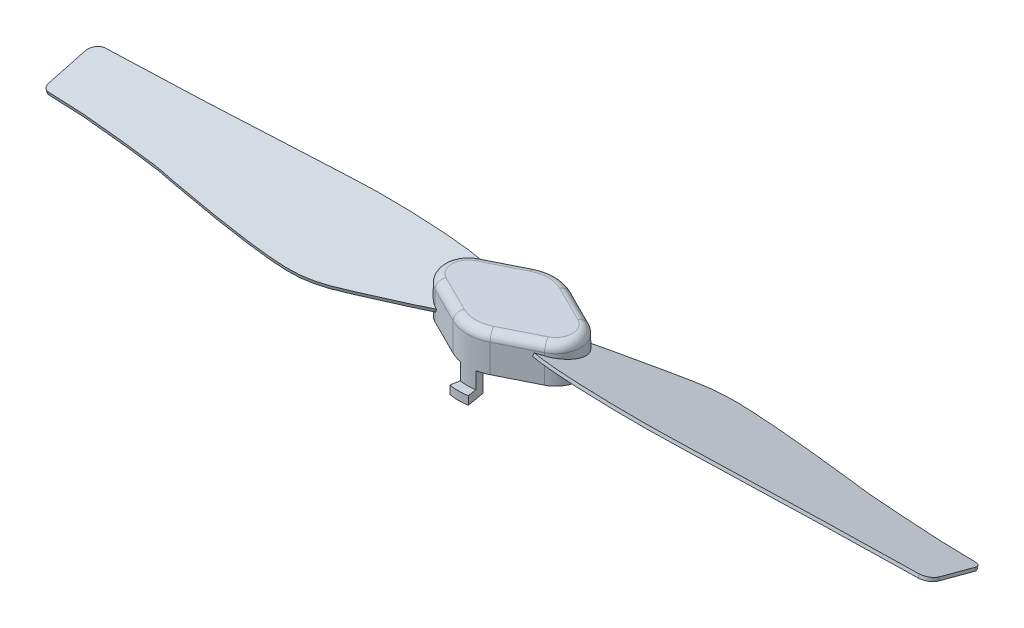
SolidWorks part; units mm, degrees
ref_plane "前视基准面" through (0, 0, 0) normal (0, 0, 1) x (1, 0, 0)
ref_plane "上视基准面" through (0, 0, 0) normal (0, 1, 0) x (1, 0, 0)
ref_plane "右视基准面" through (0, 0, 0) normal (1, 0, 0) x (0, 0, -1)
sketch "草图1" plane through (0, 0, 0) normal (0, 1, 0) x (1, 0, 0)
  line L0 (-6, 0) -> (6, 0) construction
  line L1 (0, 3) -> (0, -3) construction
  line L2 (0, 3) -> (-6, 0)
  line L3 (0, -3) -> (-6, 0)
  line L4 (0, -3) -> (6, 0)
  line L5 (6, 0) -> (0, 3)
  point P4 (0, 0)
  point P7 (0, 0)
  dimension "D1" = 12
  dimension "D2" = 6
extrude "凸台-拉伸1" add sketch "草图1" along normal blind 3.2 from offset 2
sketch "草图2" plane through (0, 2, 0) normal (0, -1, 0) x (1, 0, 0)
  line L0 (-5.2231, 0) -> (5.5973, 0)
ref_plane "基准面1" through (0, 1.866, 0.5) normal (0, -0.9659, -0.2588) x (1, 0, 0)
ref_plane "基准面10" through (0, 3.7979, 1.0176) normal (0, -0.9659, -0.2588) x (1, 0, 0)
sketch "草图9" plane through (0, 3.7979, 1.0176) normal (0, -0.9659, -0.2588) x (1, 0, 0)
  line L0 (-26.7041, 0.3228) -> (-26.7041, -1.9457)
  line L1 (0, -3.4154) -> (-6, -0.5176) construction
  line L2 (-5.2231, -0.5176) -> (5.5973, -0.5176) construction
  arc A0 (-26.7041, 0.3228) -> (-26.3393, 0.6876) centre (-26.3393, 0.3228) cw
  arc A1 (-26.7041, -1.9457) -> (-26.1115, -2.5991) centre (-26.0475, -1.9457) ccw
  spline S0 degree 3 poles (-1.4329, -0.5176) (-2.7254, 0.2749) (-2.9583, 0.3643) (-7.6949, 1.9383) (-9.1523, 2.4326) (-12.9904, 2.1706) (-15.9072, 1.7478) (-19.0984, 1.266) (-18.8037, 1.1973) (-24.7636, 0.7055) (-25.802, 0.7264) (-26.3393, 0.6876) knots 0 0 0 0 0.27319 0.324145 0.488947 0.531153 0.703993 0.748506 0.931769 0.959209 1 1 1 1
  spline S1 degree 3 poles (-26.1115, -2.5991) (-22.9105, -2.689) (-24.116, -2.6478) (-17.5523, -2.8675) (-13.3297, -3.0646) (-9.2951, -3.2316) (-3.3383, -3.0619) (-1.3944, -1.9668) (2.5094, 0.1061) (-1.4329, -0.5176) knots 0 0 0 0 0.213914 0.269576 0.524729 0.582278 0.787522 0.818456 1 1 1 1
extrude "凸台-拉伸3" add sketch "草图9" along normal mid plane 0.2
sketch "草图10" plane through (0, 0, 0) normal (1, 0, 0) x (0, 0, -1)
  line L0 (0, 4.3399) -> (0, -0.6481) construction
pattern_circular "阵列(圆周)1" count 2 over 360 about axis through (0, 4.3399, 0) along (0, -1, 0) of "凸台-拉伸3" reverse direction yes
scale "缩放比例1" bodies to scale 111 110 scale about origin uniform scaling yes scale factor 2
fillet "圆角4" radius 3 4 edges at (-12, 9.3741, 0) (12, 9.3741, 0) (-12, 5.967, 0) (12, 5.967, 0)
fillet "圆角5" radius 5 2 edges at (0, 7.2, 6) (0, 7.2, -6)
fillet "圆角6" radius 1 8 edges at (-8.2918, 10.4, 0) (-4.4348, 10.4, -3.7826) (0, 10.4, -5.4098) (4.4348, 10.4, -3.7826) (8.2918, 10.4, 0) (4.4348, 10.4, 3.7826) (0, 10.4, 5.4098) (-4.4348, 10.4, 3.7826)
sketch "草图15" plane through (0, 4, 0) normal (0, -1, 0) x (1, 0, 0)
  line L0 (-0.9382, -5.321) -> (0, 0)
  line L1 (-0.9382, 5.321) -> (0, 0)
  line L2 (0, 0) -> (0.9382, 5.321)
  line L3 (0, 0) -> (0.9382, -5.321)
  line L4 (6.6334, 2.6833) -> (2.2361, 4.882)
  line L5 (-2.2361, 4.882) -> (-6.6334, 2.6833)
  line L6 (-6.6334, -2.6833) -> (-2.2361, -4.882)
  line L7 (2.2361, -4.882) -> (6.6334, -2.6833)
  line L8 (6.6334, 2.6833) -> (2.2361, 4.882)
  line L9 (-2.2361, 4.882) -> (-6.6334, 2.6833)
  line L10 (-6.6334, -2.6833) -> (-2.2361, -4.882)
  line L11 (2.2361, -4.882) -> (6.6334, -2.6833)
  line L12 (0, -1.76) -> (0, 1.76) construction
  circle A0 centre (0, 0) radius 4.3
  arc A4 (2.2361, 4.882) -> (-2.2361, 4.882) centre (0, 0.4098) ccw
  arc A5 (-6.6334, 2.6833) -> (-6.6334, -2.6833) centre (-5.2918, 0) ccw
  arc A6 (-2.2361, -4.882) -> (2.2361, -4.882) centre (0, -0.4098) ccw
  arc A7 (6.6334, -2.6833) -> (6.6334, 2.6833) centre (5.2918, 0) ccw
  arc A8 (2.2361, 4.882) -> (-2.2361, 4.882) centre (0, 0.4098) ccw
  arc A9 (-6.6334, 2.6833) -> (-6.6334, -2.6833) centre (-5.2918, 0) ccw
  arc A10 (-2.2361, -4.882) -> (2.2361, -4.882) centre (0, -0.4098) ccw
  arc A11 (6.6334, -2.6833) -> (6.6334, 2.6833) centre (5.2918, 0) ccw
  line M10 (6.6334, 2.6833) -> (2.2361, 4.882)
  arc M11 (2.2361, 4.882) -> (-2.2361, 4.882) centre (0, 0.4098) ccw
  line M12 (-2.2361, 4.882) -> (-6.6334, 2.6833)
  arc M13 (-6.6334, 2.6833) -> (-6.6334, -2.6833) centre (-5.2918, 0) ccw
  line M14 (-6.6334, -2.6833) -> (-2.2361, -4.882)
  arc M15 (-2.2361, -4.882) -> (2.2361, -4.882) centre (0, -0.4098) ccw
  line M16 (2.2361, -4.882) -> (6.6334, -2.6833)
  arc M17 (6.6334, -2.6833) -> (6.6334, 2.6833) centre (5.2918, 0) ccw
  dimension "D2" = 8.6
  dimension "D3" = 10
  dimension "D4" = 10
  dimension "D5" = 10
  dimension "D6" = 10
  dimension "D1" = 0
extrude "切除-拉伸2" cut sketch "草图15" against normal blind 2 contours A0 L3 L2 M15 M16 M17 M10 M11 | L3 A0 L2 | L2 A0 L1 | L0 A0 L3 | L1 A0 L0 | A0 L1 L0 M11 M12 M13 M14 M15 region at (-4.9466, 4, 0) region at (-2.0219, 4, 0) region at (0, 4, -2.8521) region at (4.9466, 4, 0) region at (0, 4, 2.8521) region at (2.0219, 4, 0)
sketch "草图17" plane through (0, 4, 0) normal (0, -1, 0) x (1, 0, 0)
  line L0 (-1.1287, 6.4013) -> (1.1287, -6.4013)
  line L1 (1.1287, 6.4013) -> (-1.1287, -6.4013)
  line L2 (0, -1.76) -> (0, 1.76) construction
  circle A0 centre (0, 0) radius 6.5
  arc A1 (0.9382, 5.321) -> (-0.9382, 5.321) centre (0, 0.4098) ccw construction
  arc A2 (0.9382, 5.321) -> (-0.9382, 5.321) centre (0, 0.4098) ccw
  arc A3 (-0.9382, -5.321) -> (0.9382, -5.321) centre (0, -0.4098) ccw construction
  arc A4 (-0.9382, -5.321) -> (0.9382, -5.321) centre (0, -0.4098) ccw
  arc A5 (-0.7467, -4.2347) -> (0.7467, -4.2347) centre (0, 0) ccw construction
  arc A6 (-0.7467, -4.2347) -> (0.7467, -4.2347) centre (0, 0) ccw
  arc A7 (0.7467, 4.2347) -> (-0.7467, 4.2347) centre (0, 0) ccw construction
  arc A8 (0.7467, 4.2347) -> (-0.7467, 4.2347) centre (0, 0) ccw
  line M3 (0.7467, 4.2347) -> (0.9382, 5.321)
  arc M4 (0.9382, 5.321) -> (-0.9382, 5.321) centre (0, 0.4098) ccw
  line M5 (-0.9382, 5.321) -> (-0.7467, 4.2347)
  arc M6 (-0.7467, 4.2347) -> (0.7467, 4.2347) centre (0, 0) cw
  dimension "D1" = 13
  dimension "D2" = 10
  dimension "D3" = 10
extrude "凸台-拉伸4" add sketch "草图17" along normal blind 1 contours L1 A0 L0 M4 | M6 M3 M4 M5 | A4 L1 A0 L0 | A6 L1 A4 L0 region at (0, 4, 5.9402) region at (0, 4, 4.8502) region at (0, 4, -5.9402) region at (0, 4, -4.8502)
scale "缩放比例2" scale about centroid uniform scaling yes scale factor 1.2
sketch "草图11" [suppressed] plane through (0, 0, 0) normal (0, -1, 0) x (1, 0, 0)
  circle A0 centre (0, 0) radius 1
  dimension "D1" = 2
extrude "切除-拉伸1" cut sketch "草图11" against normal blind 10
